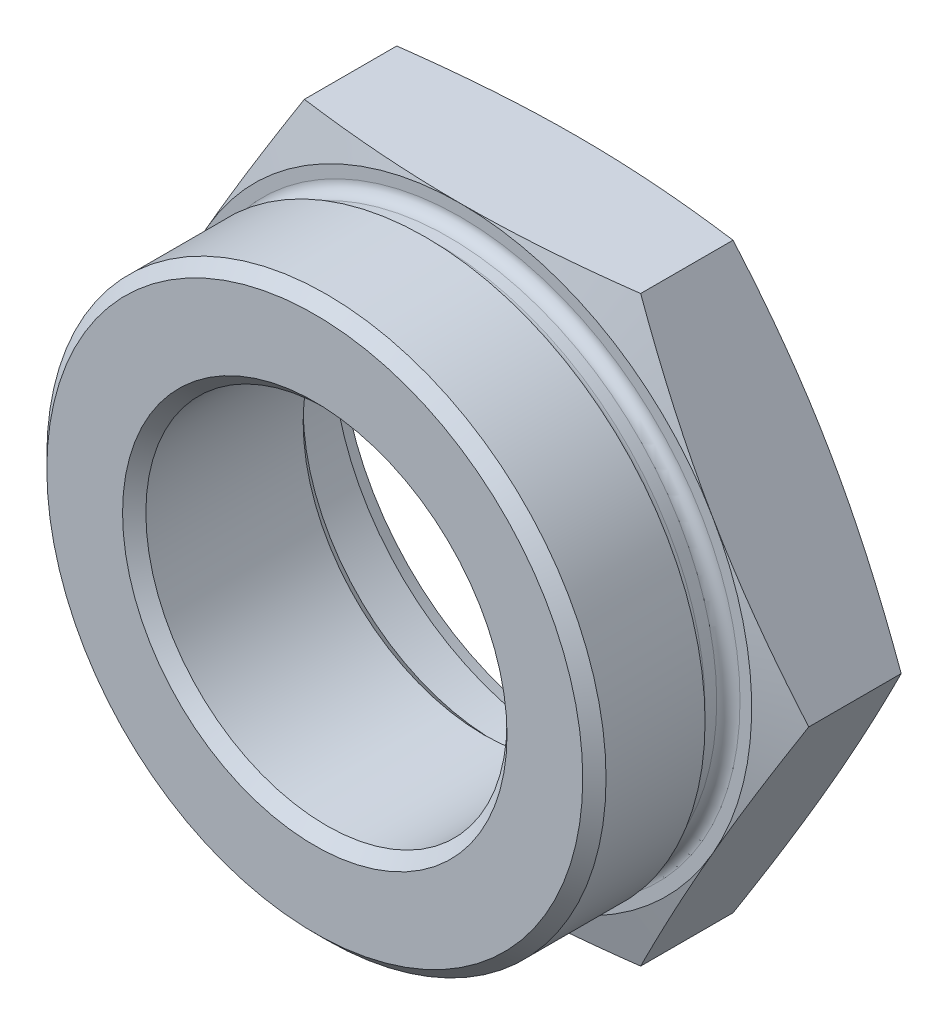
SolidWorks part; units mm, degrees
material "Plain Carbon Steel"
ref_plane "Front" through (0, 0, 0) normal (0, 0, 1) x (1, 0, 0)
ref_plane "Top" through (0, 0, 0) normal (0, 1, 0) x (1, 0, 0)
ref_plane "Right" through (0, 0, 0) normal (1, 0, 0) x (0, 0, -1)
ref_axis "Axis1" through (-84.4107, 0, 0) along (1, 0, 0)
ref_axis "Axis2" through (0, 64.3378, 0) along (0, -1, 0)
ref_axis "Axis3" through (0, 0, -102.329) along (0, 0, 1)
sketch "Sketch1" plane through (0, 0, 0) normal (0, 0, 1) x (1, 0, 0)
  line L1 (28.8675, 0) -> (14.4338, 25)
  line L2 (14.4338, 25) -> (-14.4338, 25)
  line L3 (-14.4338, 25) -> (-28.8675, 0)
  line L4 (-28.8675, 0) -> (-14.4338, -25)
  line L5 (-14.4338, -25) -> (14.4338, -25)
  line L6 (14.4338, -25) -> (28.8675, 0)
  circle A0 centre (0, 0) radius 25 construction
  dimension "D1" = 50
extrude "Boss-Extrude1" add sketch "Sketch1" along normal blind 10
sketch "Sketch2" plane through (0, 0, 10) normal (0, 0, 1) x (1, 0, 0)
  circle A0 centre (0, 0) radius 24
  dimension "D1" = 48
extrude "Boss-Extrude2" add sketch "Sketch2" along normal blind 12.5
sketch "Sketch3" plane through (0, 0, 0) normal (0, 0, -1) x (-1, 0, 0)
  circle A0 centre (0, 0) radius 20
  dimension "D1" = 40
extrude "Cut-Extrude1" cut sketch "Sketch3" against normal blind 7
sketch "Sketch4" plane through (0, 0, 7) normal (0, 0, -1) x (-1, 0, 0)
  circle A0 centre (0, 0) radius 15.5
  dimension "D1" = 31
extrude "Cut-Extrude2" cut sketch "Sketch4" against normal up to next
chamfer "Chamfer1" distance 1 angle 45 3 edges at (24, 0, 22.5) (15.5, 0, 22.5) (-15.5, 0, 7)
chamfer "Chamfer2" distance 1 angle 15 1 edges at (-20, 0, 0) first distance on face at (-20, 0, 7)
sketch "Sketch5" plane through (0, 0, 0) normal (0, 1, 0) x (1, 0, 0)
  line L0 (25, -10) -> (28.8675, -8.9637)
  line L1 (24, -10) -> (23, -10)
  line L2 (24, -10) -> (24, -13)
  line L3 (24, -13) -> (23, -13)
  line L4 (23, -10) -> (23, -13)
  line L5 (28.8675, -10) -> (14.4338, -10) construction
  line L6 (28.8675, -10) -> (28.8675, 0) construction
  line L7 (28.8675, -8.9637) -> (28.8675, -10)
  line L8 (28.8675, -10) -> (25, -10)
  line L9 (28.8675, 0) -> (28.8675, -1.0363)
  line L10 (28.8675, -1.0363) -> (25, 0)
  line L11 (28.8675, 0) -> (14.4338, 0) construction
  line L12 (25, 0) -> (28.8675, 0)
  dimension "D1" = 3
  dimension "D2" = 1
  dimension "D3" = 1
  dimension "D4" = 0
  dimension "D5" = 165
  dimension "D6" = 165
revolve "Cut-Revolve1" cut sketch "Sketch5" angle 360 about axis through (0, 0, -102.329) along (0, 0, 1)
fillet "Fillet1" radius 1 2 edges at (-23, 0, 13) (-23, 0, 10)
ref_plane "Plane1" through (0, 0, 10) normal (0, 0, 1) x (1, 0, 0)
